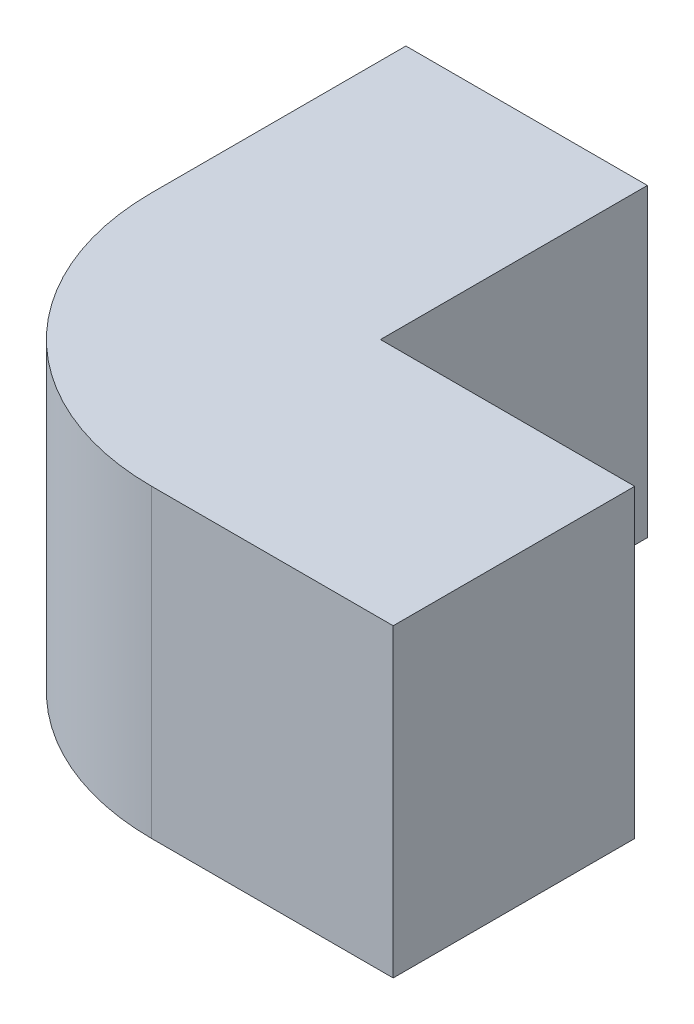
SolidWorks part; units mm, degrees
ref_plane "前视基准面" through (0, 0, 0) normal (0, 0, 1) x (1, 0, 0)
ref_plane "上视基准面" through (0, 0, 0) normal (0, 1, 0) x (1, 0, 0)
ref_plane "右视基准面" through (0, 0, 0) normal (1, 0, 0) x (0, 0, -1)
other "Configuration Table"
sketch "草图1" plane through (0, 0, 0) normal (0, 0, 1) x (1, 0, 0)
  line L1 (0, 0) -> (3.8, 0)
  line L2 (0, 0) -> (0, -4.8)
  line L3 (0, -4.8) -> (3.8, -4.8)
  line L4 (3.8, 0) -> (3.8, -4.8)
  dimension "D1" = 3.8
  dimension "D2" = 4.8
extrude "凸台-拉伸1" add sketch "草图1" along normal blind 8
sketch "草图2" plane through (3.8, 0, 0) normal (1, 0, 0) x (0, 0, -1)
  line L1 (-8, 0) -> (-4.2, 0)
  line L2 (-8, 0) -> (-8, -4.8)
  line L3 (-8, -4.8) -> (-4.2, -4.8)
  line L4 (-4.2, 0) -> (-4.2, -4.8)
  point P5 (-4, -4.8)
  dimension "D1" = 3.8
  dimension "D2" = 4.8
extrude "凸台-拉伸2" add sketch "草图2" along normal blind 4
fillet "圆角2" radius 4 1 edges at (0, -2.4, 8)
